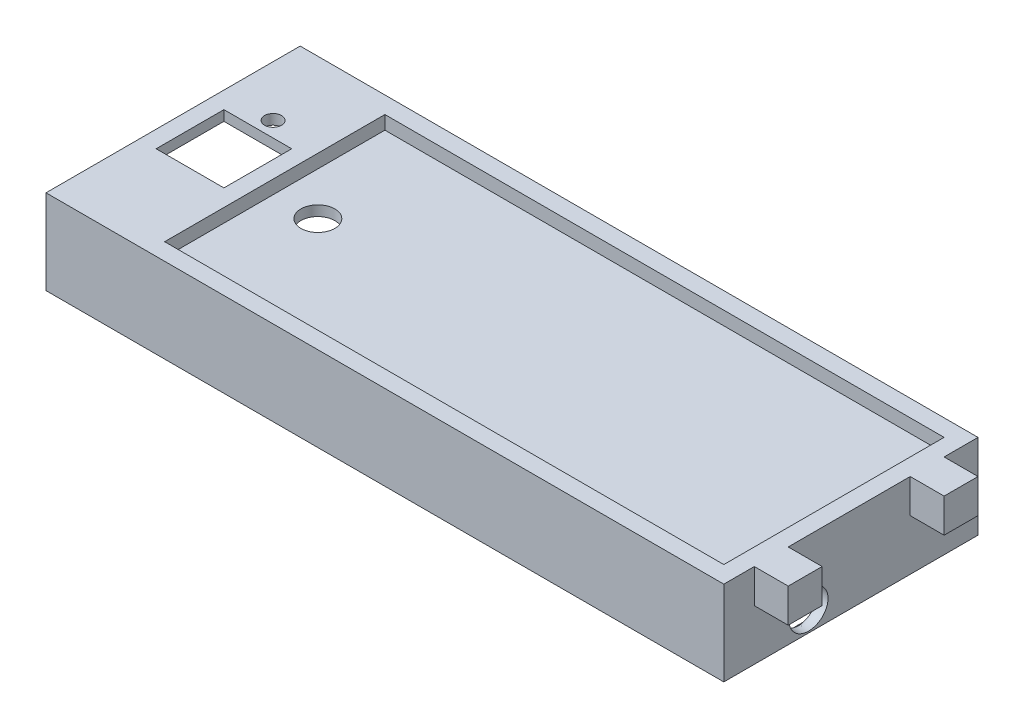
SolidWorks part; units mm, degrees
ref_plane "Front Plane" through (0, 0, 0) normal (0, 0, 1) x (1, 0, 0)
ref_plane "Top Plane" through (0, 0, 0) normal (0, 1, 0) x (1, 0, 0)
ref_plane "Right Plane" through (0, 0, 0) normal (1, 0, 0) x (0, 0, -1)
sketch "Sketch1" plane through (0, 0, 0) normal (0, 1, 0) x (1, 0, 0)
  line L1 (-60, 37.5) -> (140, 37.5)
  line L2 (-60, 37.5) -> (-60, -37.5)
  line L3 (-60, -37.5) -> (140, -37.5)
  line L4 (140, 37.5) -> (140, -37.5)
  point P0 (0, 0)
  dimension "D1" = 200
  dimension "D2" = 75
extrude "Boss-Extrude1" add sketch "Sketch1" along normal blind 25
sketch "Sketch9" plane through (0, 25, 0) normal (0, 1, 0) x (1, 0, 0)
  line L1 (-30, 32.5) -> (135, 32.5)
  line L2 (-30, 32.5) -> (-30, -32.5)
  line L3 (-30, -32.5) -> (135, -32.5)
  line L4 (135, 32.5) -> (135, -32.5)
  line L5 (140, -37.5) -> (140, 37.5) construction
  point P4 (135, 0)
  dimension "D1" = 165
  dimension "D2" = 65
  dimension "D3" = 0
  dimension "D4" = 5
extrude "Cut-Extrude5" cut sketch "Sketch9" against normal blind 4
shell "Shell3" thickness 3 removed face at (40, 0, 0) removed face at (-60, 12.5, 0)
sketch "Sketch14" plane through (140, 0, 0) normal (1, 0, 0) x (0, 0, -1)
  line L0 (37.5, 25) -> (37.5, 0) construction
  line L1 (-28.5, 25) -> (-18.5, 25)
  line L2 (-28.5, 25) -> (-28.5, 15)
  line L3 (-28.5, 15) -> (-18.5, 15)
  line L4 (-18.5, 25) -> (-18.5, 15)
  line L5 (17.5, 25) -> (27.5, 25)
  line L6 (17.5, 25) -> (17.5, 15)
  line L7 (17.5, 15) -> (27.5, 15)
  line L8 (27.5, 25) -> (27.5, 15)
  line L9 (-37.5, 25) -> (37.5, 25) construction
  dimension "D1" = 10
  dimension "D2" = 10
  dimension "D3" = 10
  dimension "D4" = 36
extrude "Boss-Extrude5" add sketch "Sketch14" along normal blind 10
sketch "Sketch15" plane through (0, 21, 0) normal (0, 1, 0) x (1, 0, 0)
  circle A0 centre (-17.2823, 0) radius 5
extrude "Cut-Extrude7" cut sketch "Sketch15" against normal through all
sketch "Sketch16" plane through (0, 25, 0) normal (0, 1, 0) x (1, 0, 0)
  line L0 (-30, 32.5) -> (-30, -32.5) construction
  line L1 (-55, -10) -> (-35, -10)
  line L2 (-55, -10) -> (-55, 10)
  line L3 (-55, 10) -> (-35, 10)
  line L4 (-35, -10) -> (-35, 10)
  line L5 (-55, -10) -> (-35, 10) construction
  line L6 (-55, 10) -> (-35, -10) construction
  line L7 (-60, -37.5) -> (140, -37.5) construction
  line L8 (140, 37.5) -> (-60, 37.5) construction
  point P0 (-45, 0)
  dimension "D1" = 20
  dimension "D2" = 20
  dimension "D3" = 5
  dimension "D4" = 27.5
  dimension "D5" = 27.5
extrude "Cut-Extrude8" cut sketch "Sketch16" against normal through all
ref_plane "Plane1" through (0, 0, 0) normal (0, 0, -1) x (-1, 0, 0)
sketch "Sketch19" plane through (140, 0, 0) normal (1, 0, 0) x (0, 0, -1)
  line L1 (-37.5, 0) -> (37.5, 0) construction
  line L3 (-37.5, 25) -> (-37.5, 0) construction
  ellipse E0 centre (-12.5, 6) end of major axis (-6.75, 6) minor radius 5.5
  dimension "D1" = 6
  dimension "D2" = 25
  dimension "D3" = 11.5
  dimension "D4" = 11
sketch "Sketch20" plane through (0, 0, 0) normal (0, 0, -1) x (-1, 0, 0)
  line L1 (-137, 18) -> (-137, 0) construction
  spline S0 degree 2 poles (-140, 6) (-136.1989, 6.6303) (-133.0758, 4.1829) knots 0 0 0 1 1 1
sweep "Cut-Sweep2" cut profiles "Sketch19" path "Sketch20"
sketch "Sketch21" plane through (0, 25, 0) normal (0, 1, 0) x (1, 0, 0)
  line L0 (-55, 0) -> (-35, 0)
  line L1 (-55, 10) -> (-55, -10) construction
  line L2 (-35, -10) -> (-35, 10) construction
  line L3 (-45, 0) -> (-45, 14.5)
  circle A0 centre (-45, 14.5) radius 2.5
  dimension "D1" = 14.5
extrude "Cut-Extrude9" cut sketch "Sketch21" against normal through all contours A0
